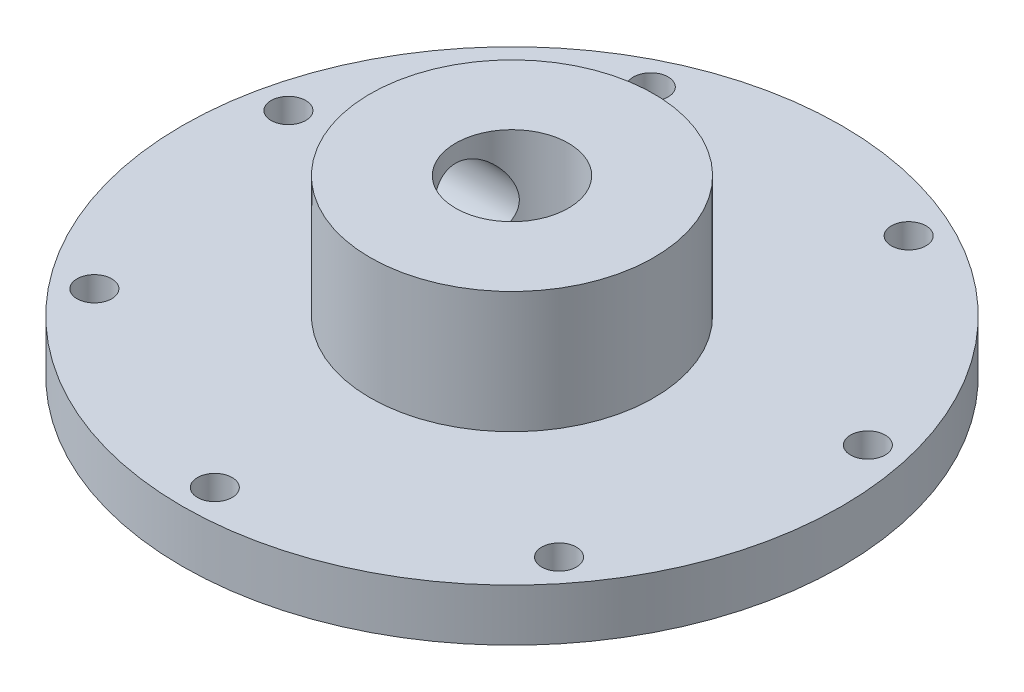
SolidWorks part; units mm, degrees
ref_plane "Front Plane" through (0, 0, 0) normal (0, 0, 1) x (1, 0, 0)
ref_plane "Top Plane" through (0, 0, 0) normal (0, 1, 0) x (1, 0, 0)
ref_plane "Right Plane" through (0, 0, 0) normal (1, 0, 0) x (0, 0, -1)
sketch "Sketch1" plane through (0, 0, 0) normal (0, 1, 0) x (1, 0, 0)
  circle A0 centre (0, 0) radius 3.25
  circle A1 centre (0, 0) radius 8.175
  circle A2 centre (0, 0) radius 19
  point P25 (0, 0)
extrude "Boss-Extrude1" add sketch "Sketch1" along normal blind 7 and the other way blind 3 contours A1 A0 region at (-7.9438, 0, 0)
extrude "Boss-Extrude2" add sketch "Sketch1<3>" against normal blind 3 separate body contours A2 A1 region at (-18.4626, 0, 0)
sketch "Sketch1<3>" plane through (0, 0, 0) normal (0, 1, 0) x (1, 0, 0) same geometry as "Sketch1"
sketch "Sketch2" plane through (0, 0, 0) normal (1, 0, 0) x (0, 0, -1)
  line L0 (0, 1) -> (0, 0)
  circle A0 centre (0, 3.5) radius 2.5
  dimension "D1" = 1
extrude "Cut-Extrude1" cut sketch "Sketch2" against normal blind 15 contours A0
sketch "Sketch3" plane through (0, -3, 0) normal (0, -1, 0) x (1, 0, 0)
  circle A1 centre (0, 17.1255) radius 1
  circle A2 centre (13.3892, 10.6776) radius 1
  circle A3 centre (16.6961, -3.8108) radius 1
  circle A4 centre (7.4305, -15.4295) radius 1
  circle A5 centre (-7.4305, -15.4295) radius 1
  circle A6 centre (-16.6961, -3.8108) radius 1
  circle A7 centre (-13.3892, 10.6776) radius 1
  point P14 (0, 0)
  dimension "D1" = 7
extrude "Cut-Extrude2" cut sketch "Sketch3" against normal through all and the other way blind 3.175
sketch "Sketch4" plane through (0, -3, 0) normal (0, -1, 0) x (1, 0, 0)
  circle A0 centre (0, 0) radius 4.175
extrude "Boss-Extrude4" add sketch "Sketch4" along normal blind 5 contours A0
extrude "Cut-Extrude3" cut sketch "Sketch1<5>" against normal blind 13 and the other way blind 15 contours A0
sketch "Sketch1<5>" plane through (0, 0, 0) normal (0, 1, 0) x (1, 0, 0) same geometry as "Sketch1"
